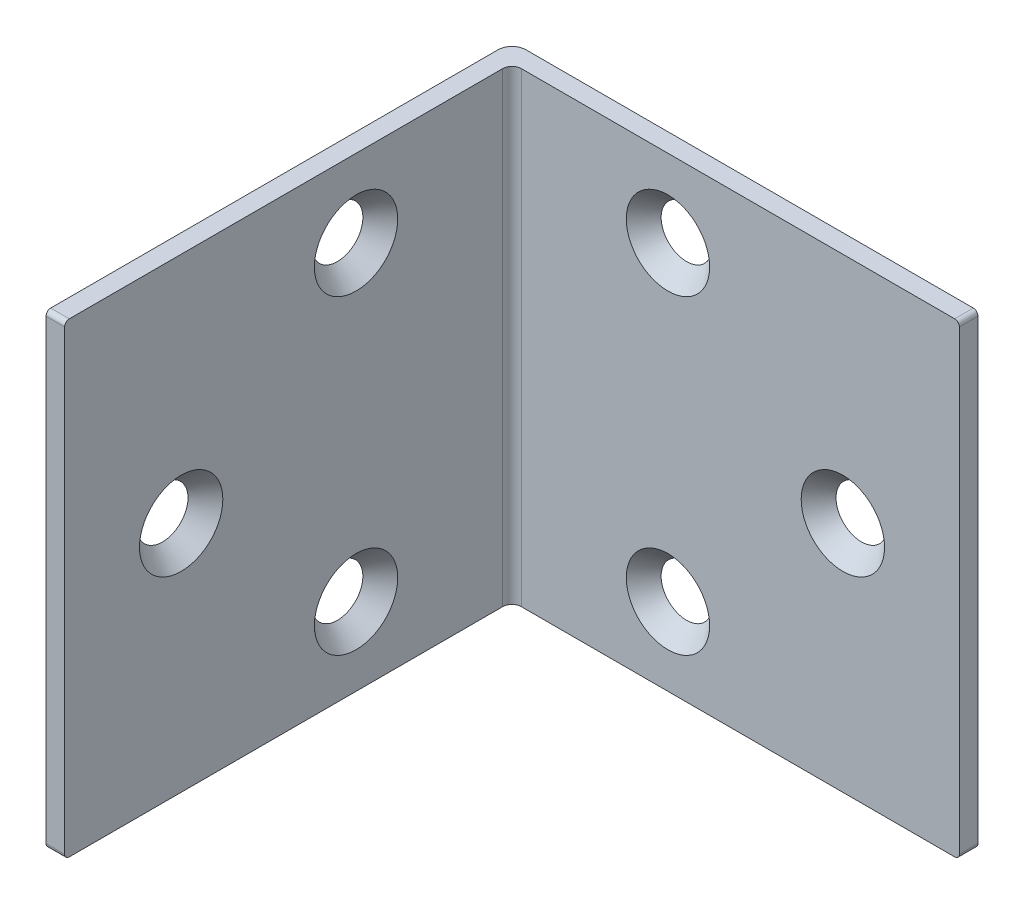
SolidWorks part; units mm, degrees
ref_plane "Front Plane" through (0, 0, 0) normal (0, 0, 1) x (1, 0, 0)
ref_plane "Top Plane" through (0, 0, 0) normal (0, 1, 0) x (1, 0, 0)
ref_plane "Right Plane" through (0, 0, 0) normal (1, 0, 0) x (0, 0, -1)
sketch "Sketch1" plane through (0, 0, 0) normal (0, 1, 0) x (1, 0, 0)
  line L0 (0, 0) -> (0, -37.338) construction
  line L1 (0, 0) -> (37.338, 0) construction
  line L2 (-0.762, -37.338) -> (0.762, -37.338) construction
  line L3 (37.338, -0.762) -> (37.338, 0.762) construction
  line L4 (37.338, 0.762) -> (-0.762, 0.762) construction
  line L5 (-0.762, 0.762) -> (-0.762, -37.338) construction
  line L6 (0.762, -37.338) -> (0.762, -0.762) construction
  line L7 (0.762, -0.762) -> (37.338, -0.762) construction
  point P7 (0, -37.338)
  point P10 (37.338, 0)
  dimension "Length (A)" = 38.1
  dimension "Length (B)" = 38.1
  dimension "Thickness" = 1.524
sketch "Sketch2" plane through (0, 0, 0) normal (1, 0, 0) x (0, 0, -1)
  line L0 (0, -19.05) -> (0, 19.05) construction
  line L2 (0.762, 0) -> (-37.338, 0) construction
  line L3 (-13.5128, -12.7) -> (-13.5128, 12.7) construction
  line L4 (-15.5956, 12.7) -> (-11.43, 12.7) construction
  point P5 (-27.813, 0)
  point P6 (0, 0)
  point P10 (-13.5128, 0)
  point P13 (-13.5128, 12.7)
  dimension "Length (C)" = 38.1
  dimension "Hole Diameter" = 4.1656
  dimension "Hole Center" = 9.525
  dimension "Horizontal Center to Center" = 14.3002
  dimension "Vertical Center to Center" = 25.4
sketch "Sketch3" plane through (0, 0, 0) normal (0, 1, 0) x (1, 0, 0)
  line L0 (0.762, -0.762) -> (37.338, -0.762) construction
  line L1 (37.338, -0.762) -> (37.338, 0.762) construction
  line L2 (0.762, -37.338) -> (0.762, -0.762) construction
  line L3 (-0.762, -37.338) -> (0.762, -37.338) construction
  line L4 (-0.762, 0.762) -> (-0.762, -37.338) construction
  line L5 (37.338, 0.762) -> (-0.762, 0.762) construction
  line L6 (0.762, -0.762) -> (37.338, -0.762)
  line L7 (37.338, -0.762) -> (37.338, 0.762)
  line L8 (0.762, -37.338) -> (0.762, -0.762)
  line L9 (-0.762, -37.338) -> (0.762, -37.338)
  line L10 (-0.762, 0.762) -> (-0.762, -37.338)
  line L11 (37.338, 0.762) -> (-0.762, 0.762)
extrude "Boss-Extrude1" add sketch "Sketch3" along normal mid plane 38.1
fillet "Fillet1" radius 1.143 1 edges at (-0.762, 0, -0.762)
fillet "Fillet2" radius 0.762 1 edges at (0.762, 0, 0.762)
fillet "Fillet3" radius 0.381 4 edges at (37.338, -19.05, 0) (37.338, 19.05, 0) (0, -19.05, 37.338) (0, 19.05, 37.338)
sketch "Sketch4" plane through (-0.762, 0, 0) normal (1, 0, 0) x (0, 0, -1)
  line L0 (-15.5956, 12.7) -> (-11.43, 12.7) construction
  circle A0 centre (-27.813, 0) radius 2.0828
  circle A1 centre (-13.5128, 12.7) radius 2.0828
  circle A2 centre (-13.5128, -12.7) radius 2.0828
extrude "Cut-Extrude1" cut sketch "Sketch4" along normal up to next (1.524 mm away) draft 41 draft outward yes
sketch "Sketch5" plane through (0, 0, -0.762) normal (0, 0, 1) x (1, 0, 0)
  line L0 (0.762, 0) -> (37.338, 0) construction
  line L2 (37.338, 18.669) -> (37.338, -18.669) construction
  circle A0 centre (13.5128, 12.7) radius 2.0828
  circle A1 centre (13.5128, -12.7) radius 2.0828
  circle A2 centre (27.813, 0) radius 2.0828
  dimension "D1" = 4.1656
  dimension "D2" = 9.525
  dimension "D3" = 14.3002
extrude "Cut-Extrude2" cut sketch "Sketch5" along normal up to next (1.524 mm away) draft 41 draft outward yes
sketch "Sketch6" plane through (0, 0, 0.762) normal (0, 0, 1) x (1, 0, 0)
  line L0 (13.5128, 12.7) -> (13.5128, 16.1076) construction
  line L1 (13.5128, 12.7) -> (15.9223, 15.1095) construction
  circle A0 centre (13.5128, 12.7) radius 3.4076 construction
  point P7 (15.9223, 15.1095)
  point P8 (13.5128, 16.1076)
  dimension "D1" = 45
equation "\"D1@Boss-Extrude1\"=\"Length (C)@Sketch2\""
equation "\"D1@Fillet1\"=\"Thickness@Sketch1\"*.75"
equation "\"D1@Fillet2\"=\"Thickness@Sketch1\"*.5"
equation "\"D1@Fillet3\"=\"Thickness@Sketch1\"*.25"
equation "\"D1@Sketch5\"=\"Hole Diameter@Sketch2\""
equation "\"D2@Sketch5\"=\"Hole Center@Sketch2\""
equation "\"D3@Sketch5\"=\"Horizontal Center to Center@Sketch2\""
